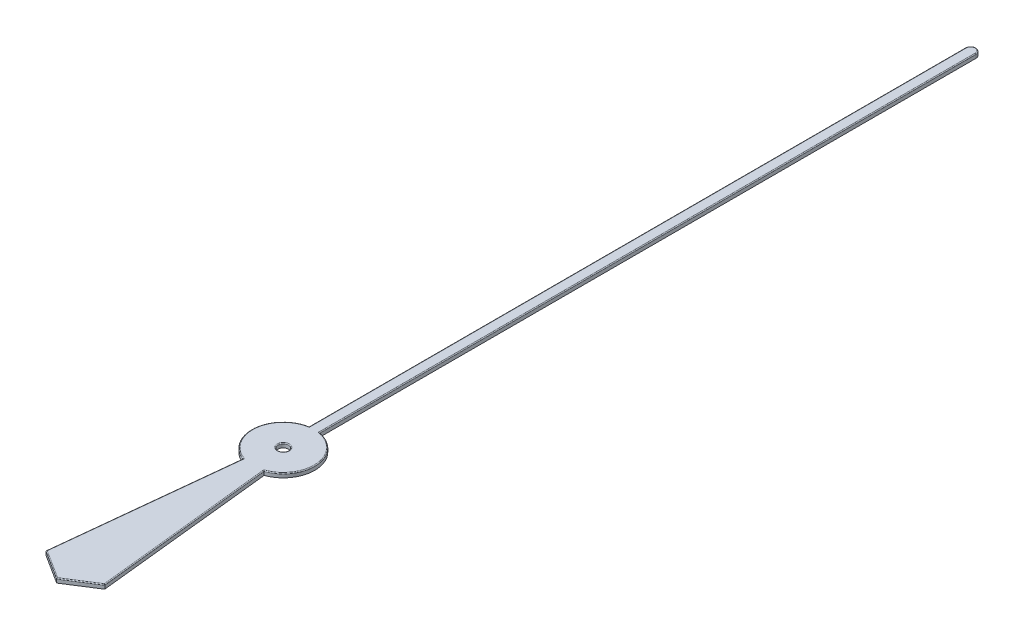
SolidWorks part; units mm, degrees
ref_plane "前视基准面" through (0, 0, 0) normal (0, 0, 1) x (1, 0, 0)
ref_plane "上视基准面" through (0, 0, 0) normal (0, 1, 0) x (1, 0, 0)
ref_plane "右视基准面" through (0, 0, 0) normal (1, 0, 0) x (0, 0, -1)
sketch "草图1" plane through (0, 0, 0) normal (0, 1, 0) x (1, 0, 0)
  circle A0 centre (0, 0) radius 21
  dimension "D1" = 42
sketch "草图3" plane through (0, 0, 0) normal (0, 1, 0) x (1, 0, 0)
  line L0 (0, 0) -> (0, 16.5) construction
  line L1 (0, 0) -> (0, -5.4) construction
  line L2 (0.125, 0.7395) -> (0.125, 16.5)
  line L3 (-0.125, 0.7395) -> (-0.125, 16.5)
  line L4 (-0.25, -0.7071) -> (-0.7, -4.9541)
  line L5 (-0.7, -4.9541) -> (0, -5.4)
  line L6 (0.7, -4.9541) -> (0, -5.4)
  line L7 (0.25, -0.7071) -> (0.7, -4.9541)
  line L8 (-0.125, 16.5) -> (0.125, 16.5)
  line L10 (-0.125, 0) -> (-0.125, 16.5) construction
  line L11 (0.125, 0) -> (0.125, 16.5) construction
  arc A0 (0.25, -0.7071) -> (0.125, 0.7395) centre (0, 0) ccw
  arc A1 (-0.125, 0.7395) -> (-0.25, -0.7071) centre (0, 0) ccw
  circle A2 centre (0, 0) radius 0.125
  dimension "D1" = 1.5
  dimension "D9" = 0.25
  dimension "D2" = 16.5
  dimension "D3" = 5.4
  dimension "D6" = 0.5
  dimension "D7" = 1.4
  dimension "D8" = 115
  dimension "D4" = 0.125
  dimension "D5" = 0.125
extrude "凸台-拉伸1" add sketch "草图3" along normal blind 0.1
fillet "圆角1" radius 0.125 2 edges at (-0.125, 0.05, -16.5) (0.125, 0.05, -16.5)
fillet "圆角2" radius 0.02 11 edges at (0, 0.1, 0.125) (0.125, 0.1, -8.5573) (0.7472, 0.1, -0.0646) (0.475, 0.1, 2.8306) (0.35, 0.1, 5.177) (-0.35, 0.1, 5.177) (-0.475, 0.1, 2.8306) (-0.7472, 0.1, -0.0646) (-0.125, 0.1, -8.5573) (-0.0884, 0.1, -16.4634) (0.0884, 0.1, -16.4634)
